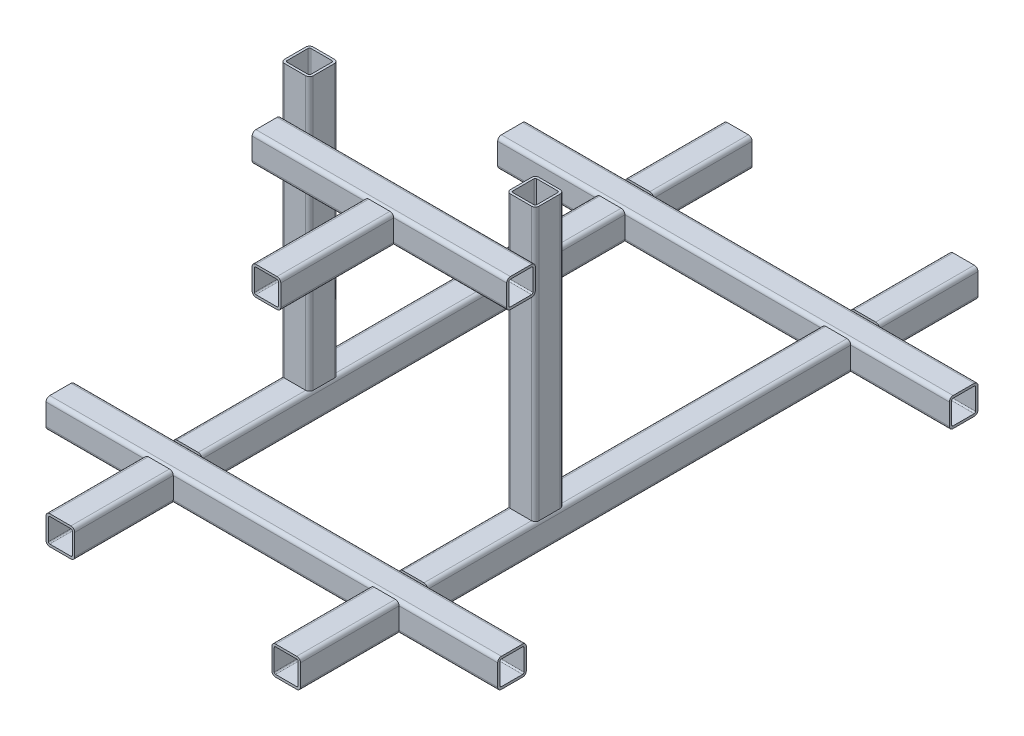
SolidWorks part; units mm, degrees
ref_plane "Front Plane" through (0, 0, 0) normal (0, 0, 1) x (1, 0, 0)
ref_plane "Top Plane" through (0, 0, 0) normal (0, 1, 0) x (1, 0, 0)
ref_plane "Right Plane" through (0, 0, 0) normal (1, 0, 0) x (0, 0, -1)
ref_plane "Bottom Face" through (0, 0, 0) normal (0, 1, 0) x (1, 0, 0)
ref_plane "Top Face" through (0, 38.1, 0) normal (0, 1, 0) x (1, 0, 0)
ref_plane "Mid Plane" through (0, 19.05, 0) normal (0, 1, 0) x (1, 0, 0)
ref_plane "Front Face" through (0, 0, 450) normal (0, 0, 1) x (1, 0, 0)
ref_plane "Back Face" through (0, 0, -450) normal (0, 0, 1) x (1, 0, 0)
ref_plane "Left Face" through (300, 0, 0) normal (1, 0, 0) x (0, 0, -1)
ref_plane "Right Face" through (-300, 0, 0) normal (1, 0, 0) x (0, 0, -1)
ref_plane "Divider Plane" through (0, 0, 100) normal (0, 0, 1) x (1, 0, 0)
ref_plane "Max Height Plane" through (0, 400, 0) normal (0, 1, 0) x (1, 0, 0)
ref_plane "Electronics Box Plane" through (0, 338.1, 0) normal (0, 1, 0) x (1, 0, 0)
sketch "Sketch2" plane through (300, 0, 0) normal (1, 0, 0) x (0, 0, -1)
  line L0 (330, 38.1) -> (-330, 38.1) construction
  line L5 (330, 0) -> (-330, 0) construction
  line L6 (0, 220) -> (0, -220) construction
  line L7 (-314.05, 38.1) -> (-285.95, 38.1)
  line L8 (-280.95, 33.1) -> (-280.95, 5)
  line L9 (-315.875, 33.1) -> (-315.875, 5)
  line L10 (-314.05, 3.175) -> (-285.95, 3.175)
  line L11 (-285.95, 0) -> (-314.05, 0)
  line L12 (-319.05, 5) -> (-319.05, 33.1)
  line L13 (-300, 38.1) -> (-300, 0) construction
  line L14 (-319.05, 19.05) -> (-280.95, 19.05) construction
  line L15 (-284.125, 5) -> (-284.125, 33.1)
  line L16 (-285.95, 34.925) -> (-314.05, 34.925)
  line L17 (-300, 34.925) -> (-300, 3.175) construction
  line L18 (-315.875, 19.05) -> (-284.125, 19.05) construction
  arc A0 (-285.95, 38.1) -> (-280.95, 33.1) centre (-285.95, 33.1) cw
  arc A1 (-280.95, 5) -> (-285.95, 0) centre (-285.95, 5) cw
  arc A2 (-314.05, 0) -> (-319.05, 5) centre (-314.05, 5) cw
  arc A3 (-319.05, 33.1) -> (-314.05, 38.1) centre (-314.05, 33.1) cw
  arc A4 (-315.875, 5) -> (-314.05, 3.175) centre (-314.05, 5) ccw
  arc A5 (-285.95, 3.175) -> (-284.125, 5) centre (-285.95, 5) ccw
  arc A6 (-284.125, 33.1) -> (-285.95, 34.925) centre (-285.95, 33.1) ccw
  arc A7 (-314.05, 34.925) -> (-315.875, 33.1) centre (-314.05, 33.1) ccw
  point P20 (-300, 19.05)
  point P39 (-300, 19.05)
  dimension "D1" = 5
  dimension "D2" = 300
  dimension "D3" = 3.175
extrude "Front Cross-Car Member" add sketch "Sketch2" against normal up to surface (600 mm away) up to plane "Right Face"
sketch "Sketch5" plane through (300, 0, 0) normal (1, 0, 0) x (0, 0, -1)
  line L0 (285.95, 38.1) -> (314.05, 38.1)
  line L1 (319.05, 33.1) -> (319.05, 5)
  line L2 (314.05, 0) -> (285.95, 0)
  line L3 (280.95, 5) -> (280.95, 33.1)
  line L4 (300, 38.1) -> (300, 0) construction
  line L5 (280.95, 19.05) -> (319.05, 19.05) construction
  line L6 (285.95, 34.925) -> (314.05, 34.925)
  line L7 (315.875, 33.1) -> (315.875, 5)
  line L8 (314.05, 3.175) -> (285.95, 3.175)
  line L9 (284.125, 5) -> (284.125, 33.1)
  line L10 (300, 34.925) -> (300, 3.175) construction
  line L11 (284.125, 19.05) -> (315.875, 19.05) construction
  line L12 (330, 0) -> (-330, 0) construction
  line L14 (330, 38.1) -> (-330, 38.1) construction
  line L15 (0, 220) -> (0, -220) construction
  arc A0 (314.05, 38.1) -> (319.05, 33.1) centre (314.05, 33.1) cw
  arc A1 (319.05, 5) -> (314.05, 0) centre (314.05, 5) cw
  arc A2 (285.95, 0) -> (280.95, 5) centre (285.95, 5) cw
  arc A3 (280.95, 33.1) -> (285.95, 38.1) centre (285.95, 33.1) cw
  arc A4 (314.05, 34.925) -> (315.875, 33.1) centre (314.05, 33.1) cw
  arc A5 (315.875, 5) -> (314.05, 3.175) centre (314.05, 5) cw
  arc A6 (285.95, 3.175) -> (284.125, 5) centre (285.95, 5) cw
  arc A7 (284.125, 33.1) -> (285.95, 34.925) centre (285.95, 33.1) cw
  point P32 (300, 19.05)
  point P33 (300, 19.05)
  dimension "D2" = 5
  dimension "D1" = 3.175
  dimension "D3" = 300
extrude "Back Cross-Car Member" add sketch "Sketch5" against normal up to surface (600 mm away) separate body up to plane "Right Face"
sketch "Sketch6" plane through (0, 0, -450) normal (0, 0, 1) x (1, 0, 0)
  line L0 (135.95, 38.1) -> (164.05, 38.1)
  line L1 (169.05, 33.1) -> (169.05, 5)
  line L2 (134.125, 33.1) -> (134.125, 5)
  line L3 (135.95, 3.175) -> (164.05, 3.175)
  line L4 (164.05, 0) -> (135.95, 0)
  line L5 (130.95, 5) -> (130.95, 33.1)
  line L6 (150, 38.1) -> (150, 0) construction
  line L7 (130.95, 19.05) -> (169.05, 19.05) construction
  line L8 (165.875, 5) -> (165.875, 33.1)
  line L9 (164.05, 34.925) -> (135.95, 34.925)
  line L10 (150, 34.925) -> (150, 3.175) construction
  line L11 (134.125, 19.05) -> (165.875, 19.05) construction
  line L12 (330, 38.1) -> (-330, 38.1) construction
  line L13 (330, 0) -> (-330, 0) construction
  line L14 (0, -220) -> (0, 220) construction
  arc A0 (164.05, 38.1) -> (169.05, 33.1) centre (164.05, 33.1) cw
  arc A1 (169.05, 5) -> (164.05, 0) centre (164.05, 5) cw
  arc A2 (135.95, 0) -> (130.95, 5) centre (135.95, 5) cw
  arc A3 (130.95, 33.1) -> (135.95, 38.1) centre (135.95, 33.1) cw
  arc A4 (134.125, 5) -> (135.95, 3.175) centre (135.95, 5) ccw
  arc A5 (164.05, 3.175) -> (165.875, 5) centre (164.05, 5) ccw
  arc A6 (165.875, 33.1) -> (164.05, 34.925) centre (164.05, 33.1) ccw
  arc A7 (135.95, 34.925) -> (134.125, 33.1) centre (135.95, 33.1) ccw
  point P16 (150, 19.05)
  point P33 (150, 19.05)
  dimension "D1" = 5
  dimension "D2" = 3.175
  dimension "D3" = 150
extrude "Back Left Along-Car Member" add sketch "Sketch6" along normal blind 130.95
extrude "Middle Left Along-Car Member" add sketch "Sketch6<2>" along normal blind 561.9 from offset 169.05
sketch "Sketch6<2>" plane through (0, 0, -450) normal (0, 0, 1) x (1, 0, 0) same geometry as "Sketch6"
extrude "Front Left Along-Car Member" add sketch "Sketch6<3>" along normal blind 130.95 from offset 769.05
sketch "Sketch6<3>" plane through (0, 0, -450) normal (0, 0, 1) x (1, 0, 0) same geometry as "Sketch6"
sketch "Sketch7" plane through (0, 0, -450) normal (0, 0, 1) x (1, 0, 0)
  line L0 (-164.05, 38.1) -> (-135.95, 38.1)
  line L1 (-130.95, 33.1) -> (-130.95, 5)
  line L2 (-165.875, 33.1) -> (-165.875, 5)
  line L3 (-164.05, 3.175) -> (-135.95, 3.175)
  line L4 (-135.95, 0) -> (-164.05, 0)
  line L5 (-169.05, 5) -> (-169.05, 33.1)
  line L6 (-150, 38.1) -> (-150, 0) construction
  line L7 (-169.05, 19.05) -> (-130.95, 19.05) construction
  line L8 (-134.125, 5) -> (-134.125, 33.1)
  line L9 (-135.95, 34.925) -> (-164.05, 34.925)
  line L10 (-150, 34.925) -> (-150, 3.175) construction
  line L11 (-165.875, 19.05) -> (-134.125, 19.05) construction
  line L12 (330, 38.1) -> (-330, 38.1) construction
  line L13 (330, 0) -> (-330, 0) construction
  line L14 (0, -220) -> (0, 220) construction
  arc A0 (-135.95, 38.1) -> (-130.95, 33.1) centre (-135.95, 33.1) cw
  arc A1 (-130.95, 5) -> (-135.95, 0) centre (-135.95, 5) cw
  arc A2 (-164.05, 0) -> (-169.05, 5) centre (-164.05, 5) cw
  arc A3 (-169.05, 33.1) -> (-164.05, 38.1) centre (-164.05, 33.1) cw
  arc A4 (-165.875, 5) -> (-164.05, 3.175) centre (-164.05, 5) ccw
  arc A5 (-135.95, 3.175) -> (-134.125, 5) centre (-135.95, 5) ccw
  arc A6 (-134.125, 33.1) -> (-135.95, 34.925) centre (-135.95, 33.1) ccw
  arc A7 (-164.05, 34.925) -> (-165.875, 33.1) centre (-164.05, 33.1) ccw
  point P16 (-150, 19.05)
  point P33 (-150, 19.05)
  dimension "D1" = 5
  dimension "D2" = 3.175
  dimension "D3" = 150
extrude "Back Right Along-Car Member" add sketch "Sketch7" along normal blind 130.95
extrude "Middle Right Along-Car Member" add sketch "Sketch7<2>" along normal blind 561.9 from offset 169.05
sketch "Sketch7<2>" plane through (0, 0, -450) normal (0, 0, 1) x (1, 0, 0) same geometry as "Sketch7"
extrude "Front Right Along-Car Member" add sketch "Sketch7<3>" along normal blind 130.95 from offset 769.05
sketch "Sketch7<3>" plane through (0, 0, -450) normal (0, 0, 1) x (1, 0, 0) same geometry as "Sketch7"
sketch "Sketch8" plane through (0, 38.1, 0) normal (0, 1, 0) x (1, 0, 0)
  line L0 (-164.05, -100) -> (-135.95, -100)
  line L1 (-130.95, -105) -> (-130.95, -133.1)
  line L2 (-165.875, -105) -> (-165.875, -133.1)
  line L3 (-164.05, -134.925) -> (-135.95, -134.925)
  line L4 (-135.95, -138.1) -> (-164.05, -138.1)
  line L5 (-169.05, -133.1) -> (-169.05, -105)
  line L6 (-150, -100) -> (-150, -138.1) construction
  line L7 (-169.05, -119.05) -> (-130.95, -119.05) construction
  line L8 (-134.125, -133.1) -> (-134.125, -105)
  line L9 (-135.95, -103.175) -> (-164.05, -103.175)
  line L10 (-150, -103.175) -> (-150, -134.925) construction
  line L11 (-165.875, -119.05) -> (-134.125, -119.05) construction
  line L12 (-220, -100) -> (220, -100) construction
  line L13 (0, -220) -> (0, 220) construction
  arc A0 (-135.95, -100) -> (-130.95, -105) centre (-135.95, -105) cw
  arc A1 (-130.95, -133.1) -> (-135.95, -138.1) centre (-135.95, -133.1) cw
  arc A2 (-164.05, -138.1) -> (-169.05, -133.1) centre (-164.05, -133.1) cw
  arc A3 (-169.05, -105) -> (-164.05, -100) centre (-164.05, -105) cw
  arc A4 (-165.875, -133.1) -> (-164.05, -134.925) centre (-164.05, -133.1) ccw
  arc A5 (-135.95, -134.925) -> (-134.125, -133.1) centre (-135.95, -133.1) ccw
  arc A6 (-134.125, -105) -> (-135.95, -103.175) centre (-135.95, -105) ccw
  arc A7 (-164.05, -103.175) -> (-165.875, -105) centre (-164.05, -105) ccw
  point P16 (-150, -119.05)
  point P33 (-150, -119.05)
  dimension "D1" = 5
  dimension "D2" = 3.175
  dimension "D3" = 38.1
  dimension "D4" = 150
extrude "Right Vertical Member" add sketch "Sketch8" along normal up to surface (361.9 mm away) up to plane "Max Height Plane"
sketch "Sketch10" plane through (0, 38.1, 0) normal (0, 1, 0) x (1, 0, 0)
  line L0 (135.95, -100) -> (164.05, -100)
  line L1 (169.05, -105) -> (169.05, -133.1)
  line L2 (134.125, -105) -> (134.125, -133.1)
  line L3 (135.95, -134.925) -> (164.05, -134.925)
  line L4 (164.05, -138.1) -> (135.95, -138.1)
  line L5 (130.95, -133.1) -> (130.95, -105)
  line L6 (150, -100) -> (150, -138.1) construction
  line L7 (130.95, -119.05) -> (169.05, -119.05) construction
  line L8 (165.875, -133.1) -> (165.875, -105)
  line L9 (164.05, -103.175) -> (135.95, -103.175)
  line L10 (150, -103.175) -> (150, -134.925) construction
  line L11 (134.125, -119.05) -> (165.875, -119.05) construction
  line L12 (-220, -100) -> (220, -100) construction
  line L13 (0, -220) -> (0, 220) construction
  arc A0 (164.05, -100) -> (169.05, -105) centre (164.05, -105) cw
  arc A1 (169.05, -133.1) -> (164.05, -138.1) centre (164.05, -133.1) cw
  arc A2 (135.95, -138.1) -> (130.95, -133.1) centre (135.95, -133.1) cw
  arc A3 (130.95, -105) -> (135.95, -100) centre (135.95, -105) cw
  arc A4 (134.125, -133.1) -> (135.95, -134.925) centre (135.95, -133.1) ccw
  arc A5 (164.05, -134.925) -> (165.875, -133.1) centre (164.05, -133.1) ccw
  arc A6 (165.875, -105) -> (164.05, -103.175) centre (164.05, -105) ccw
  arc A7 (135.95, -103.175) -> (134.125, -105) centre (135.95, -105) ccw
  point P16 (150, -119.05)
  point P33 (150, -119.05)
  dimension "D1" = 5
  dimension "D2" = 3.175
  dimension "D3" = 38.1
  dimension "D4" = 150
extrude "Left Vertical Member" add sketch "Sketch10" along normal up to surface (361.9 mm away) up to plane "Max Height Plane"
sketch "Sketch11" plane through (300, 0, 0) normal (1, 0, 0) x (0, 0, -1)
  line L0 (-171.2, 338.1) -> (-143.1, 338.1)
  line L1 (-138.1, 333.1) -> (-138.1, 305)
  line L2 (-173.025, 333.1) -> (-173.025, 305)
  line L3 (-171.2, 303.175) -> (-143.1, 303.175)
  line L4 (-143.1, 300) -> (-171.2, 300)
  line L5 (-176.2, 305) -> (-176.2, 333.1)
  line L6 (-157.15, 338.1) -> (-157.15, 300) construction
  line L7 (-176.2, 319.05) -> (-138.1, 319.05) construction
  line L8 (-141.275, 305) -> (-141.275, 333.1)
  line L9 (-143.1, 334.925) -> (-171.2, 334.925)
  line L10 (-157.15, 334.925) -> (-157.15, 303.175) construction
  line L11 (-173.025, 319.05) -> (-141.275, 319.05) construction
  line L12 (-100, 220) -> (-100, -220) construction
  line L13 (330, 338.1) -> (-330, 338.1) construction
  arc A0 (-143.1, 338.1) -> (-138.1, 333.1) centre (-143.1, 333.1) cw
  arc A1 (-138.1, 305) -> (-143.1, 300) centre (-143.1, 305) cw
  arc A2 (-171.2, 300) -> (-176.2, 305) centre (-171.2, 305) cw
  arc A3 (-176.2, 333.1) -> (-171.2, 338.1) centre (-171.2, 333.1) cw
  arc A4 (-173.025, 305) -> (-171.2, 303.175) centre (-171.2, 305) ccw
  arc A5 (-143.1, 303.175) -> (-141.275, 305) centre (-143.1, 305) ccw
  arc A6 (-141.275, 333.1) -> (-143.1, 334.925) centre (-143.1, 333.1) ccw
  arc A7 (-171.2, 334.925) -> (-173.025, 333.1) centre (-171.2, 333.1) ccw
  point P16 (-157.15, 319.05)
  point P33 (-157.15, 319.05)
  dimension "D1" = 5
  dimension "D2" = 3.175
  dimension "D3" = 38.1
  dimension "D4" = 38.1
extrude "Upper Cross-Car Member" add sketch "Sketch11" against normal blind 338.1 from offset 130.95 offset against normal yes
sketch "Sketch12" plane through (0, 0, 100) normal (0, 0, 1) x (1, 0, 0)
  line L0 (-14.05, 338.1) -> (14.05, 338.1)
  line L1 (19.05, 333.1) -> (19.05, 305)
  line L2 (-15.875, 333.1) -> (-15.875, 305)
  line L3 (-14.05, 303.175) -> (14.05, 303.175)
  line L4 (14.05, 300) -> (-14.05, 300)
  line L5 (-19.05, 305) -> (-19.05, 333.1)
  line L6 (0, 338.1) -> (0, 300) construction
  line L7 (-19.05, 319.05) -> (19.05, 319.05) construction
  line L8 (15.875, 305) -> (15.875, 333.1)
  line L9 (14.05, 334.925) -> (-14.05, 334.925)
  line L10 (0, 334.925) -> (0, 303.175) construction
  line L11 (-15.875, 319.05) -> (15.875, 319.05) construction
  line L12 (330, 338.1) -> (-330, 338.1) construction
  line L13 (0, -220) -> (0, 220) construction
  arc A0 (14.05, 338.1) -> (19.05, 333.1) centre (14.05, 333.1) cw
  arc A1 (19.05, 305) -> (14.05, 300) centre (14.05, 305) cw
  arc A2 (-14.05, 300) -> (-19.05, 305) centre (-14.05, 305) cw
  arc A3 (-19.05, 333.1) -> (-14.05, 338.1) centre (-14.05, 333.1) cw
  arc A4 (-15.875, 305) -> (-14.05, 303.175) centre (-14.05, 305) ccw
  arc A5 (14.05, 303.175) -> (15.875, 305) centre (14.05, 305) ccw
  arc A6 (15.875, 333.1) -> (14.05, 334.925) centre (14.05, 333.1) ccw
  arc A7 (-14.05, 334.925) -> (-15.875, 333.1) centre (-14.05, 333.1) ccw
  point P16 (0, 319.05)
  point P33 (0, 319.05)
  dimension "D1" = 5
  dimension "D2" = 3.175
  dimension "D3" = 38.1
extrude "E-Box Platform Base" add sketch "Sketch12" along normal blind 150 from offset 76.2
equation "\"D1@Front Face\" = \"frameLength@Master Assembly.Assembly\" / 2"
equation "\"D1@Back Face\" = \"frameLength@Master Assembly.Assembly\" / 2"
equation "\"D1@Left Face\"=\"frameWidth@Master Assembly.Assembly\"/2"
equation "\"D1@Right Face\" = \"frameWidth@Master Assembly.Assembly\" / 2"
equation "\"D1@Top Face\"=\"frameTubeStockHeight@Master Assembly.Assembly\""
equation "\"D2@Sketch2\"=\"frameMemberDistLength@Master Assembly.Assembly\"/2"
equation "\"D3@Sketch2\"=\"frameTubeStockWallThickness@Master Assembly.Assembly\""
equation "\"D1@Sketch5\"=\"frameTubeStockWallThickness@Master Assembly.Assembly\""
equation "\"D3@Sketch5\"=\"frameMemberDistLength@Master Assembly.Assembly\"/2"
equation "\"D3@Sketch6\"=\"frameMemberDistWidth@Master Assembly.Assembly\"/2"
equation "\"D1@Back Left Along-Car Member\"=(\"frameLength@Master Assembly.Assembly\" - \"frameMemberDistLength@Master Assembly.Assembly\" - \"frameTubeStockHeight@Master Assembly.Assembly\")  / 2"
equation "\"D19@Middle Left Along-Car Member\" = ( \"frameLength@Master Assembly.Assembly\" - \"frameMemberDistLength@Master Assembly.Assembly\" + \"frameTubeStockHeight@Master Assembly.Assembly\" ) / 2"
equation "\"D1@Middle Left Along-Car Member\"=\"frameMemberDistLength@Master Assembly.Assembly\" - \"frameTubeStockHeight@Master Assembly.Assembly\""
equation "\"D19@Front Left Along-Car Member\"=( \"frameLength@Master Assembly.Assembly\" - \"frameMemberDistLength@Master Assembly.Assembly\" )  / 2 + \"frameMemberDistLength@Master Assembly.Assembly\" + \"frameTubeStockHeight@Master Assembly.Assembly\" / 2"
equation "\"D1@Front Left Along-Car Member\"=(\"frameLength@Master Assembly.Assembly\" - \"frameMemberDistLength@Master Assembly.Assembly\" - \"frameTubeStockHeight@Master Assembly.Assembly\")  / 2"
equation "\"D3@Sketch7\"=\"frameMemberDistWidth@Master Assembly.Assembly\"/2"
equation "\"D1@Back Right Along-Car Member\"=(\"frameLength@Master Assembly.Assembly\" - \"frameMemberDistLength@Master Assembly.Assembly\" - \"frameTubeStockHeight@Master Assembly.Assembly\")  / 2"
equation "\"D19@Middle Right Along-Car Member\" = ( \"frameLength@Master Assembly.Assembly\" - \"frameMemberDistLength@Master Assembly.Assembly\" + \"frameTubeStockHeight@Master Assembly.Assembly\" ) / 2"
equation "\"D1@Middle Right Along-Car Member\"=\"frameMemberDistLength@Master Assembly.Assembly\" - \"frameTubeStockHeight@Master Assembly.Assembly\""
equation "\"D19@Front Right Along-Car Member\"=( \"frameLength@Master Assembly.Assembly\" - \"frameMemberDistLength@Master Assembly.Assembly\" )  / 2 + \"frameMemberDistLength@Master Assembly.Assembly\" + \"frameTubeStockHeight@Master Assembly.Assembly\" / 2"
equation "\"D1@Front Right Along-Car Member\"=(\"frameLength@Master Assembly.Assembly\" - \"frameMemberDistLength@Master Assembly.Assembly\" - \"frameTubeStockHeight@Master Assembly.Assembly\")  / 2"
equation "\"D1@Divider Plane\"= \"frameDividerPlaneOffset@Master Assembly.Assembly\""
equation "\"D3@Sketch8\"=\"frameTubeStockHeight@Master Assembly.Assembly\""
equation "\"D4@Sketch8\"=\"frameMemberDistWidth@Master Assembly.Assembly\"/2"
equation "\"D1@Max Height Plane\" = \"frameHeight@Master Assembly.Assembly\""
equation "\"D4@Sketch10\"=\"frameMemberDistWidth@Master Assembly.Assembly\"/2"
equation "\"D1@Electronics Box Plane\" = \"eboxPlaneHeight@Master Assembly.Assembly\""
equation "\"D4@Sketch11\"=\"frameTubeStockHeight@Master Assembly.Assembly\""
equation "\"D19@Upper Cross-Car Member\" = ( \"frameWidth@Master Assembly.Assembly\" - \"frameMemberDistWidth@Master Assembly.Assembly\" - \"frameTubeStockHeight@Master Assembly.Assembly\" ) / 2"
equation "\"D1@Upper Cross-Car Member\" = \"frameMemberDistWidth@Master Assembly.Assembly\" + \"frameTubeStockHeight@Master Assembly.Assembly\""
equation "\"D19@E-Box Platform Base\"= \"frameTubeStockHeight@Master Assembly.Assembly\" * 2"
equation "\"D2@Sketch6\"=\"frameTubeStockWallThickness@Master Assembly.Assembly\""
equation "\"D2@Sketch7\"=\"frameTubeStockWallThickness@Master Assembly.Assembly\""
equation "\"D2@Sketch8\"=\"frameTubeStockWallThickness@Master Assembly.Assembly\""
equation "\"D3@Sketch10\"=\"frameTubeStockHeight@Master Assembly.Assembly\""
equation "\"D2@Sketch10\"=\"frameTubeStockWallThickness@Master Assembly.Assembly\""
equation "\"D3@Sketch11\"=\"frameTubeStockHeight@Master Assembly.Assembly\""
equation "\"D2@Sketch11\"=\"frameTubeStockWallThickness@Master Assembly.Assembly\""
equation "\"D3@Sketch12\"=\"frameTubeStockHeight@Master Assembly.Assembly\""
equation "\"D2@Sketch12\"=\"frameTubeStockWallThickness@Master Assembly.Assembly\""
